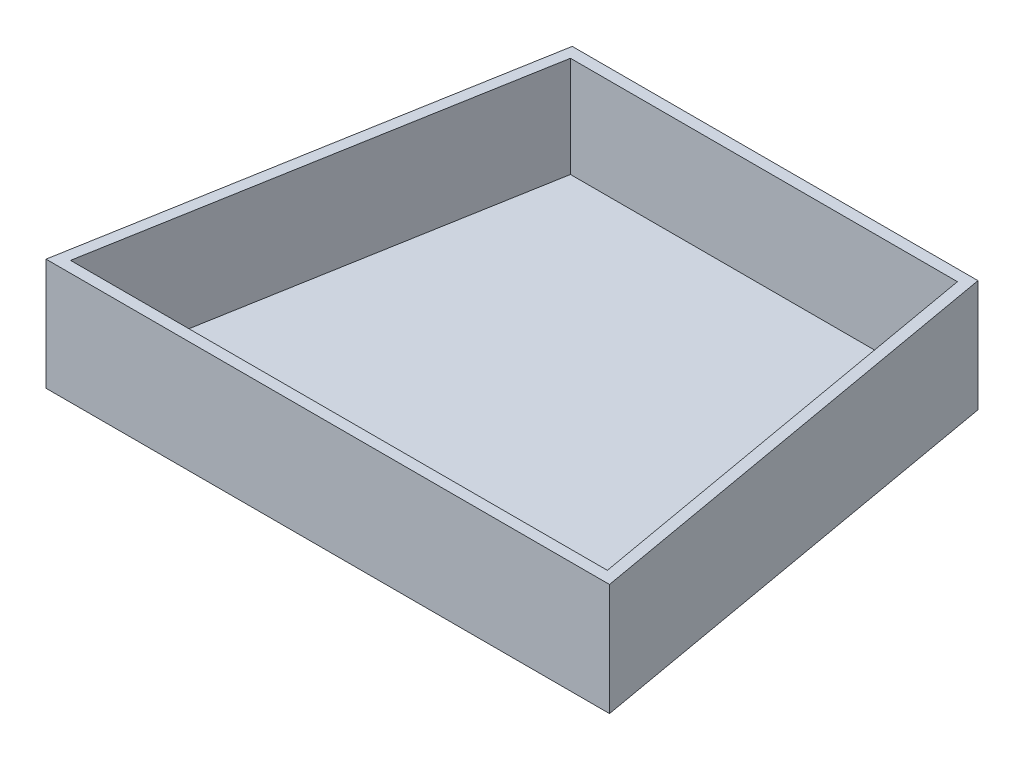
SolidWorks part; units mm, degrees
ref_plane "Front Plane" through (0, 0, 0) normal (0, 0, 1) x (1, 0, 0)
ref_plane "Top Plane" through (0, 0, 0) normal (0, 1, 0) x (1, 0, 0)
ref_plane "Right Plane" through (0, 0, 0) normal (1, 0, 0) x (0, 0, -1)
sketch "Sketch1" plane through (0, 0, 0) normal (0, 1, 0) x (1, 0, 0)
  line L0 (0, 0) -> (33.5021, 190)
  line L3 (240, 0) -> (0, 0)
  line L4 (33.5021, 190) -> (206.4979, 190)
  line L5 (206.4979, 190) -> (240, 0)
  dimension "D1" = 80
  dimension "D2" = 80
  dimension "D3" = 240
  dimension "D4" = 190
extrude "Extrude-Thin1" add sketch "Sketch1" along normal blind 50 thin contours L3 L0 L4 L5 thin type one direction wall 5
extrude "Boss-Extrude1" add sketch "Sketch1<3>" along normal blind 5 separate body
sketch "Sketch1<3>" plane through (0, 0, 0) normal (0, 1, 0) x (1, 0, 0) same geometry as "Sketch1"
